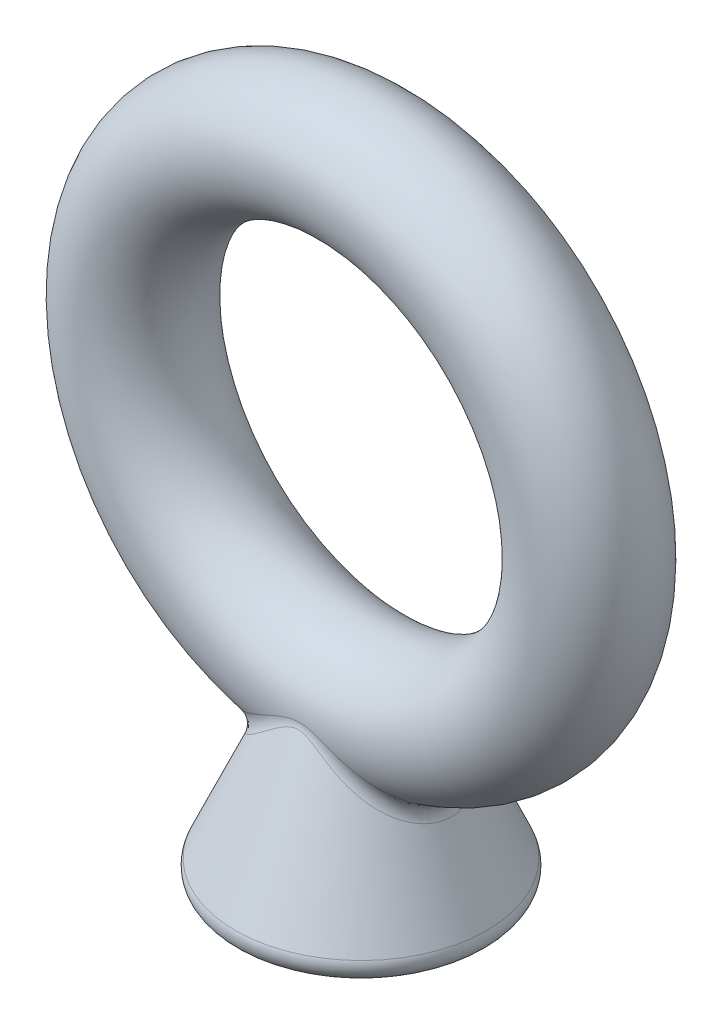
SolidWorks part; units mm, degrees
ref_plane "Front Plane" through (0, 0, 0) normal (0, 0, 1) x (1, 0, 0)
ref_plane "Top Plane" through (0, 0, 0) normal (0, 1, 0) x (1, 0, 0)
ref_plane "Right Plane" through (0, 0, 0) normal (1, 0, 0) x (0, 0, -1)
sketch "Sketch1" plane through (0, 0, 0) normal (0, 0, 1) x (1, 0, 0)
  line L0 (0, -26.1937) -> (0, -137.3188) construction
  line L1 (-6.35, -137.3188) -> (6.35, -137.3188) construction
  line L3 (0, -26.1937) -> (0, -15.0812) construction
  line L4 (-11.5094, -35.7188) -> (11.5094, -35.7188) construction
  circle A0 centre (0, 0) radius 26.1937 construction
  circle A1 centre (0, 20.6375) radius 5.5562 construction
  circle A2 centre (0, 0) radius 15.0813 construction
  point P7 (0, -26.1937)
  point P9 (0, -35.7188)
  point P10 (0, 26.1937)
  point P11 (0, 15.0812)
  point P14 (0, -137.3188)
  point P19 (0, -20.6375)
  point P21 (0, -35.7188)
  dimension "A" = 11.1125
  dimension "Eye Dia." = 30.1625
  dimension "Overall Lg." = 163.5125
  dimension "Shank Lg." = 101.6
  dimension "OD" = 52.3875
  dimension "Thread Lg." = 101.6
  dimension "Thread OD" = 12.7
  dimension "Shoulder Dia." = 23.0188
  dimension "Thickness" = 9.525
sketch "Sketch6" plane through (0, 0, 0) normal (1, 0, 0) x (0, 0, -1)
  circle A0 centre (0, 20.6375) radius 5.5563
ref_axis "Axis1" through (0, 0, -12.6603) along (0, 0, 1)
revolve "Revolve1" add sketch "Sketch6" angle 360 about axis through (0, 0, -12.6603) along (0, 0, 1)
sketch "Sketch8" plane through (0, 0, 0) normal (0, 0, 1) x (1, 0, 0)
  line L0 (0, -35.7188) -> (0, -20.6375)
  line L1 (0, -20.6375) -> (-5.5562, -20.6375)
  line L2 (-10.1203, -35.7188) -> (-11.5094, -35.7188) construction
  line L3 (-11.5094, -35.7188) -> (-11.5094, -34.3297) construction
  line L5 (-11.5094, -35.7188) -> (11.5094, -35.7188) construction
  line L6 (-11.3897, -33.7656) -> (-5.5562, -20.6375)
  line L9 (-10.1203, -35.7188) -> (0, -35.7188)
  arc A0 (-11.3897, -33.7656) -> (-10.1203, -35.7188) centre (-10.1203, -34.3297) ccw
  circle A1 centre (0, -20.6375) radius 5.5562 construction
  dimension "D1" = 1.3891
revolve "Revolve2" add sketch "Sketch8" angle 360 about L0
fillet "Fillet1" radius 1.3891 1 edges at (6.6312, -24.4646, 2.9477)
